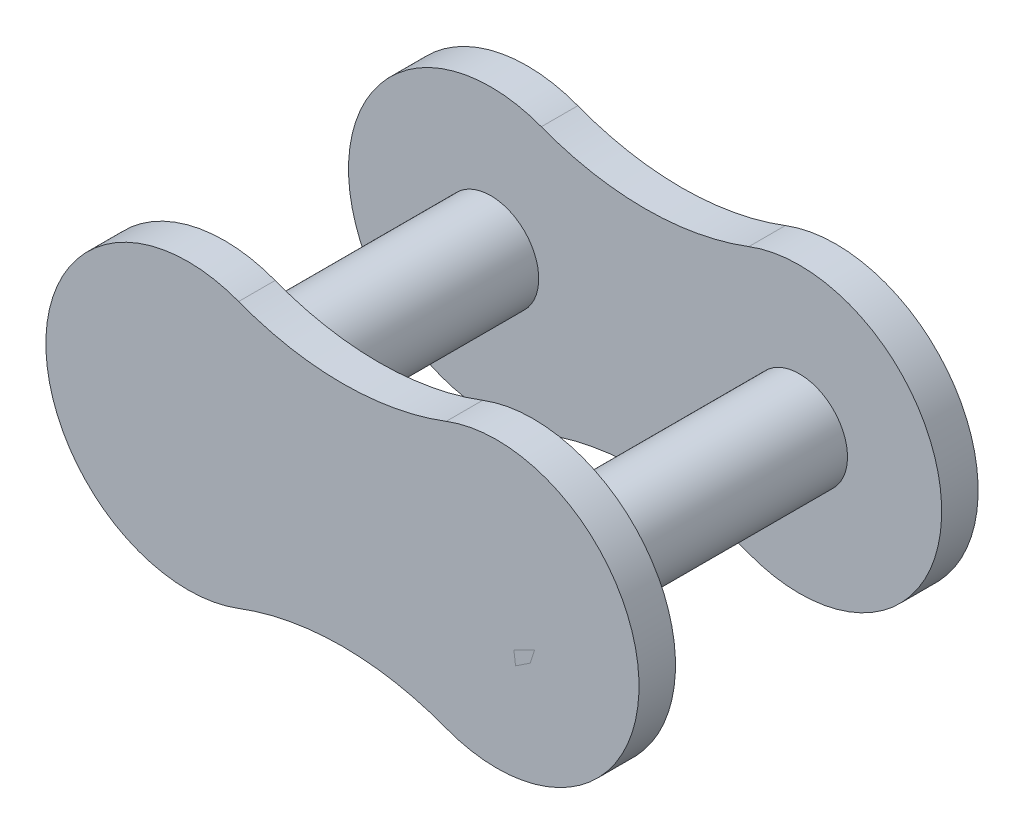
SolidWorks part; units mm, degrees
ref_plane "Front Plane" through (0, 0, 0) normal (0, 0, 1) x (1, 0, 0)
ref_plane "Top Plane" through (0, 0, 0) normal (0, 1, 0) x (1, 0, 0)
ref_plane "Right Plane" through (0, 0, 0) normal (1, 0, 0) x (0, 0, -1)
sketch "Sketch1" plane through (0, 0, 0) normal (0, 0, 1) x (1, 0, 0)
  line L0 (0, 0) -> (12.7, 0) construction
  arc A0 (2.0811, 5.4673) -> (2.0811, -5.4673) centre (0, 0) ccw
  arc A1 (10.6189, -5.4673) -> (10.6189, 5.4673) centre (12.7, 0) ccw
  arc A2 (2.0811, 5.4673) -> (10.6189, 5.4673) centre (6.35, 16.6823) ccw
  arc A3 (2.0811, -5.4673) -> (10.6189, -5.4673) centre (6.35, -16.6823) cw
  dimension "D2" = 11.7
  dimension "D3" = 11.7
  dimension "D4" = 12
  dimension "D1" = 12.7
extrude "Boss-Extrude1" add sketch "Sketch1" along normal blind 1.5
ref_plane "Plane1" through (0, 0, 6.975) normal (0, 0, 1) x (1, 0, 0)
mirror "Mirror2" about plane through (0, 0, 6.975) normal (0, 0, 1) of bodies 101
sketch "Sketch3" plane through (0, 0, 0) normal (0, 0, -1) x (-1, 0, 0)
  circle A0 centre (0, 0) radius 1.975
  circle A1 centre (-12.7, 0) radius 1.975
  dimension "D1" = 3.95
  dimension "D2" = 3.95
extrude "Boss-Extrude2" add sketch "Sketch3" against normal up to surface (13.95 mm away) separate body up to face at (6.35, 0, 13.95)
